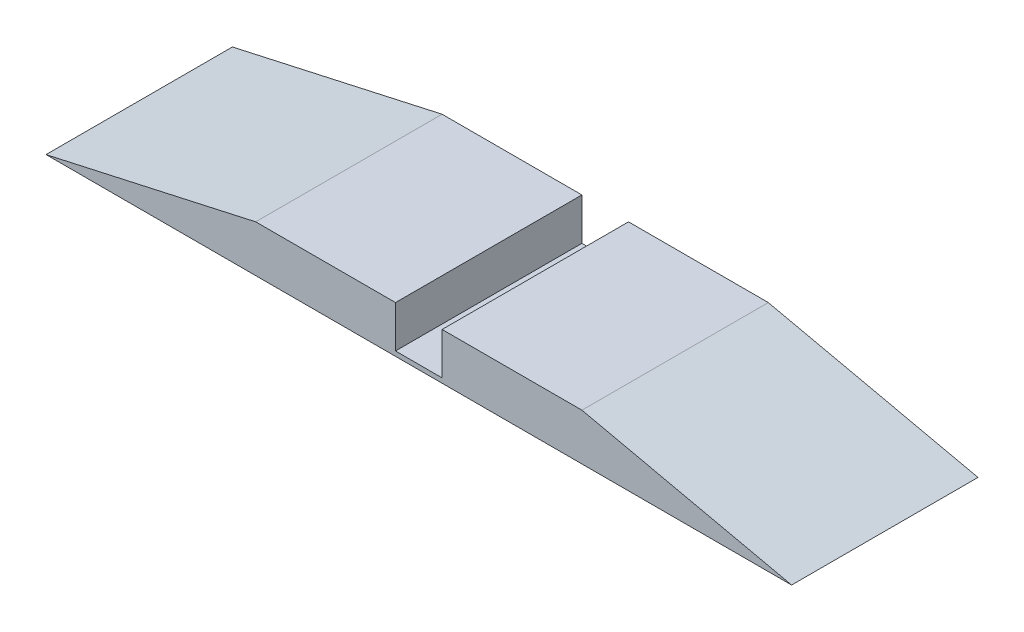
SolidWorks part; units mm, degrees
ref_plane "Front Plane" through (0, 0, 0) normal (0, 0, 1) x (1, 0, 0)
ref_plane "Top Plane" through (0, 0, 0) normal (0, 1, 0) x (1, 0, 0)
ref_plane "Right Plane" through (0, 0, 0) normal (1, 0, 0) x (0, 0, -1)
sketch "Sketch2" plane through (0, 0, 0) normal (0, 0, 1) x (1, 0, 0)
  line L0 (-1750, -275) -> (-4000, -275)
  line L1 (-250, -275) -> (250, -275)
  line L2 (-250, -225) -> (-250, 225)
  line L4 (250, -225) -> (250, 225)
  line L5 (0, 0) -> (0, -275) construction
  line L6 (-250, 0) -> (250, 0) construction
  line L7 (-250, 225) -> (-1750, 225)
  line L8 (-250, 225) -> (-250, -225)
  line L9 (-250, -275) -> (-1750, -275)
  line L11 (250, 225) -> (1750, 225)
  line L12 (250, 225) -> (250, -225)
  line L13 (250, -275) -> (1750, -275)
  line L15 (-4000, -275) -> (1750, -275)
  line L16 (1750, -275) -> (4000, -275)
  line L17 (-1750, 225) -> (-4000, -275)
  line L18 (1750, 225) -> (4000, -275)
  line L19 (-250, -225) -> (250, -225)
  point P0 (0, 0)
  dimension "D1" = 500
  dimension "D2" = 500
  dimension "D3" = 1500
  dimension "D4" = 1500
  dimension "D5" = 8000
  dimension "D6" = 4000
  dimension "D7" = 50
extrude "Boss-Extrude1" add sketch "Sketch2" along normal blind 1000 and the other way blind 1000 contours L19 L2 L7 L17 L0 L9 L1 L13 L16 L18 L11 L4 region at (-2875, -194.8439, 0)
